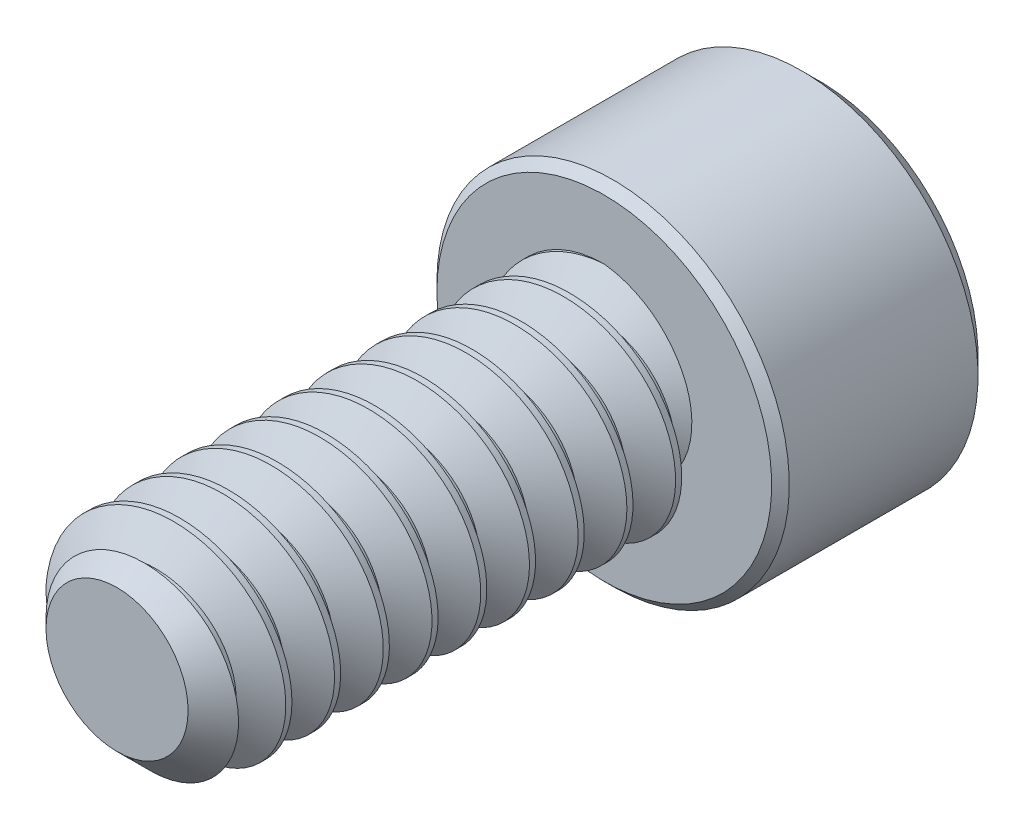
SolidWorks part; units mm, degrees
ref_plane "Front Plane" through (0, 0, 0) normal (0, 0, 1) x (1, 0, 0)
ref_plane "Top Plane" through (0, 0, 0) normal (0, 1, 0) x (1, 0, 0)
ref_plane "Right Plane" through (0, 0, 0) normal (1, 0, 0) x (0, 0, -1)
sketch "Sketch0" plane through (0, 0, 0) normal (1, 0, 0) x (0, 0, -1)
  line L0 (0, 0) -> (7.9375, 0) construction
  point P2 (11.4427, 0)
  point P4 (0, 0)
  dimension "D1" = 7.9375
  dimension "D2" = 3.5052
  dimension "Min Thread" = 0
sketch "Sketch1" plane through (0, 0, 0) normal (0, 0, 1) x (1, 0, 0)
  circle A0 centre (0, 0) radius 1.7526
  dimension "OD" = 3.5052
extrude "Extrude1" add sketch "Sketch1" against normal blind 7.9375
sketch "Sketch2" plane through (0, 0, 0) normal (0, 0, 1) x (1, 0, 0)
  circle A0 centre (0, 0) radius 1.7526 construction
  circle A1 centre (0, 0) radius 1.7526
curve "Helix/Spiral1" pitch 0.7937 height 8.7312 turns 11 parameters "pitch"=0.7937
chamfer "Chamfer3" distance 0.5953 angle 45 1 edges at (1.7526, 0, 0)
sketch "Sketch3" plane through (0, 0, 0) normal (1, 0, 0) x (0, 0, -1)
  line L0 (-0.6945, 1.7526) -> (-0.3969, 1.237)
  line L1 (-0.3969, 1.237) -> (-0.2977, 1.237)
  line L2 (-0.2977, 1.237) -> (0, 1.7526)
  line L3 (-0.6945, 1.7526) -> (0, 1.7526)
  line L4 (-0.3473, 1.7526) -> (-0.3473, 1.237) construction
  line L5 (-0.5457, 1.4948) -> (-0.1488, 1.4948) construction
  line L6 (0, 1.7526) -> (0, -1.7526) construction
  dimension "D1" = 0.0992
  dimension "D2" = 0.3969
  dimension "D3" = 60
sweep "Cut-Sweep1" cut profiles "Sketch3" path "Helix/Spiral1"
sketch "Sketch5" plane through (0, 0, 0) normal (1, 0, 0) x (0, 0, -1)
  line L0 (7.9375, -1.2539) -> (7.9375, 1.2505) construction
  line L1 (7.9375, 1.7526) -> (0, 1.7526)
  line L2 (7.9375, 1.7526) -> (7.9375, 0)
  line L3 (7.9375, 0) -> (-0.6379, 0)
  line L4 (0, 0) -> (7.9375, 0) construction
  line L5 (0, 1.7526) -> (-0.6379, 0)
  line L6 (0, 0) -> (10.4775, 0) construction
  dimension "D1" = 70
  dimension "D3" = 2.54
revolve "partially thread" [suppressed] add sketch "Sketch5" angle 360 about L6
sketch "Sketch6" plane through (0, 0, -7.9375) normal (0, 0, -1) x (-1, 0, 0)
  circle A0 centre (0, 0) radius 2.8702
  dimension "head dia" = 5.7404
extrude "Extrude2" add sketch "Sketch6" along normal blind 3.5052
sketch "Sketch7" plane through (0, 0, -11.4427) normal (0, 0, -1) x (-1, 0, 0)
  line L1 (0, 1.604) -> (-1.3891, 0.802)
  line L2 (-1.3891, 0.802) -> (-1.3891, -0.802)
  line L3 (-1.3891, -0.802) -> (0, -1.604)
  line L4 (0, -1.604) -> (1.3891, -0.802)
  line L5 (1.3891, -0.802) -> (1.3891, 0.802)
  line L6 (1.3891, 0.802) -> (0, 1.604)
  circle A0 centre (0, 0) radius 1.3891 construction
  dimension "hex dia" = 2.7781
extrude "Cut-Extrude1" cut sketch "Sketch7" against normal blind 2.0836
sketch "Sketch8" plane through (0, 0, -11.4427) normal (0, 0, -1) x (-1, 0, 0)
  circle A0 centre (0, 0) radius 1.604
extrude "Cut-Extrude2" cut sketch "Sketch8" against normal through all draft 45
chamfer "Chamfer1" distance 0.287 angle 45 1 edges at (-2.8702, 0, -11.4427)
chamfer "Chamfer2" distance 0.1435 angle 45 1 edges at (-2.8702, 0, -7.9375)
sketch "Sketch9" plane through (0, 0, 0) normal (1, 0, 0) x (0, 0, -1)
  line L0 (0, 1.7526) -> (0, -1.7526) construction
  line L1 (1.9844, 1.7526) -> (1.9844, -1.7526) construction
  line L2 (11.4427, 2.8702) -> (11.4427, -2.8702) construction
  line L3 (7.9375, 2.8702) -> (7.9375, -2.8702) construction
  line L4 (7.9375, 2.7267) -> (7.9375, -2.7267) construction
  line L5 (11.4427, -2.5832) -> (11.4427, 2.5832) construction
  line L6 (7.9375, -2.8702) -> (7.9375, 2.8702) construction
  line L7 (0, 1.1573) -> (0, -1.1573) construction
  line L8 (-0.6945, 1.7526) -> (0, 1.7526) construction
  line L9 (1.9844, 0) -> (0, 0) construction
  dimension "D1" = 1.9844
equation "\"D3@Helix/Spiral1\" = \"screw length@Extrude1\"+\"pitch@Helix/Spiral1\""
equation "\"D1@Sketch3\" = \"pitch@Helix/Spiral1\"*.125"
equation "\"D2@Sketch3\" = \"pitch@Helix/Spiral1\"*.5"
equation "\"D1@Cut-Extrude1\" = \"hex dia@Sketch7\"*.75"
equation "\"D1@Chamfer1\" = \"head dia@Sketch6\"*.05"
equation "\"D1@Sketch9\" = \"pitch@Helix/Spiral1\"*2.50"
equation "\"D1@Chamfer2\" = \"D1@Chamfer1\"/2"
equation "\"D1@Chamfer3\" = \"pitch@Helix/Spiral1\"*.750"
equation "\"D1@Sketch0\" = \"screw length@Extrude1\""
equation "\"D2@Sketch0\" = \"head depth@Extrude2\""
